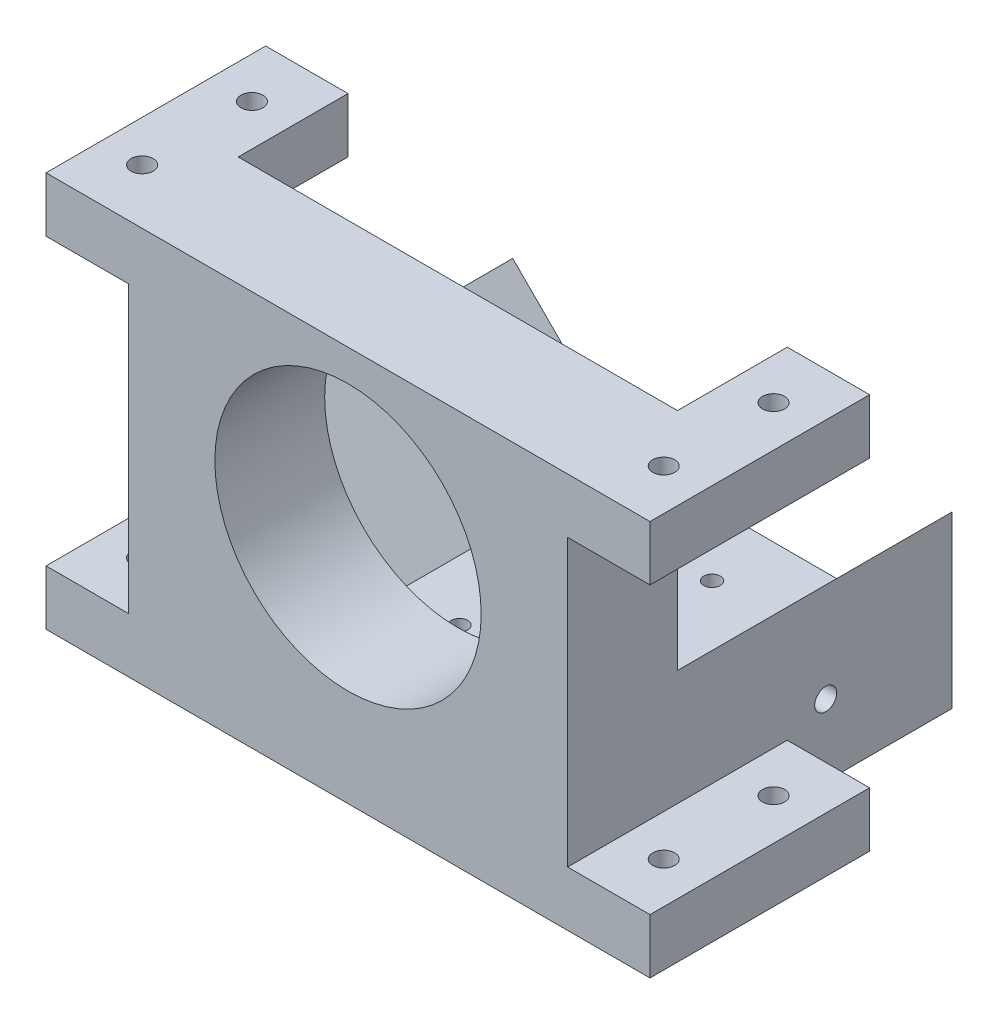
SolidWorks part; units mm, degrees
ref_plane "Front Plane" through (0, 0, 0) normal (0, 0, 1) x (1, 0, 0)
ref_plane "Top Plane" through (0, 0, 0) normal (0, 1, 0) x (1, 0, 0)
ref_plane "Right Plane" through (0, 0, 0) normal (1, 0, 0) x (0, 0, -1)
sketch "Sketch1" plane through (0, 0, 0) normal (0, 0, 1) x (1, 0, 0)
  line L1 (-40, -30) -> (40, -30)
  line L2 (-40, -30) -> (-40, 30)
  line L3 (-40, 30) -> (40, 30)
  line L4 (40, -30) -> (40, 30)
  line L5 (-40, -30) -> (40, 30) construction
  line L6 (-40, 30) -> (40, -30) construction
  circle A0 centre (0, 0) radius 24.25
  dimension "D1" = 48.5
  dimension "D2" = 80
  dimension "D3" = 60
extrude "Boss-Extrude1" add sketch "Sketch1" along normal blind 20
sketch "Sketch4" plane through (40, 0, 0) normal (1, 0, 0) x (0, 0, -1)
  line L0 (0, -30) -> (0, 30) construction
  line L1 (-20, 30) -> (0, 30)
  line L2 (-20, 30) -> (-20, 20)
  line L3 (-20, 20) -> (0, 20)
  line L5 (-20, 30) -> (0, 20) construction
  line L6 (-20, 20) -> (0, 30) construction
  line L8 (0, 30) -> (20, 30)
  line L10 (0, 20) -> (20, 20)
  line L11 (20, 30) -> (20, 20)
  line L12 (0, 30) -> (20, 20) construction
  line L13 (0, 20) -> (20, 30) construction
  point P4 (-10, 25)
  point P10 (10, 25)
  point P11 (-9.9994, 25.0003)
  point P12 (3.1904, 30)
  dimension "D1" = 10
extrude "Boss-Extrude3" add sketch "Sketch4" along normal blind 15
sketch "Sketch5" plane through (0, 30, 0) normal (0, 1, 0) x (1, 0, 0)
  line L0 (-40, -10) -> (55, -10) construction
  line L1 (55, 20) -> (55, -20) construction
  line L3 (40, 0) -> (40, -20) construction
  line L4 (40, 0) -> (-40, 0) construction
  line L5 (55, -20) -> (-40, -20) construction
  line L6 (-40, -20) -> (-40, 0) construction
  line L7 (55, 20) -> (55, -20) construction
  line L8 (40, 0) -> (55, 0) construction
  circle A0 centre (47.5, -10) radius 2
  circle A1 centre (47.5, 10) radius 2
  point P20 (0, 0)
  dimension "D1" = 4
  dimension "D2" = 7.5
extrude "Cut-Extrude2" cut sketch "Sketch5" against normal up to surface (10 mm away) up to face at (46, 20, 0)
sketch "Sketch6" plane through (0, -30, 0) normal (0, -1, 0) x (-1, 0, 0)
  line L1 (40, -20) -> (-40, -20)
  line L2 (40, -20) -> (40, 0)
  line L3 (40, 0) -> (-40, 0)
  line L4 (-40, -20) -> (-40, 0)
  line L5 (40, -20) -> (-40, 0) construction
  line L6 (40, 0) -> (-40, -20) construction
  point P4 (0, -10)
extrude "Boss-Extrude4" add sketch "Sketch6" along normal blind 2
sketch "Sketch8" plane through (0, 0, 0) normal (0, 0, -1) x (-1, 0, 0)
  line L0 (-40, -11) -> (-19, -32)
  line L1 (-40, -32) -> (-40, 20) construction
  line L2 (40, -32) -> (-40, -32) construction
  line L3 (-19, -32) -> (-40, -32)
  line L4 (-40, -32) -> (-40, -11)
  dimension "D1" = 21
extrude "Boss-Extrude6" add sketch "Sketch8" along normal blind 50
sketch "Sketch9" plane through (40, 0, 0) normal (1, 0, 0) x (0, 0, -1)
  line L0 (-20, -32) -> (-20, 20) construction
  line L1 (50, -32) -> (-20, -32) construction
  circle A0 centre (27, -29) radius 2
  dimension "D1" = 4
  dimension "D2" = 47
  dimension "D3" = 3
extrude "Cut-Extrude3" cut sketch "Sketch9" against normal through all
ref_plane "Plane1" through (19, 0, 0) normal (-1, 0, 0) x (0, 0, 1)
sketch "Sketch12" plane through (0, -32, 0) normal (0, -1, 0) x (1, 0, 0)
  line L0 (0, 20) -> (0, -50) construction
  line L1 (-40, 20) -> (40, 20)
  line L2 (-40, 20) -> (-40, -50)
  line L3 (-40, -50) -> (40, -50)
  line L4 (40, 20) -> (40, -50)
  line L5 (-40, 20) -> (40, -50) construction
  line L6 (-40, -50) -> (40, 20) construction
  line L7 (-8, -8.3) -> (8, -8.3) construction
  line L8 (-8, -8.3) -> (-8, -38.3) construction
  line L9 (-8, -38.3) -> (8, -38.3) construction
  line L10 (8, -38.3) -> (8, -8.3) construction
  line L11 (-40, 0) -> (19, 0) construction
  circle A0 centre (-8, -8.3) radius 1.5
  circle A1 centre (8, -8.3) radius 1.5
  circle A2 centre (8, -38.3) radius 1.5
  circle A3 centre (-8, -38.3) radius 1.5
  point P4 (0, -15)
  point P11 (0, -8.3)
  dimension "D4" = 3
  dimension "D1" = 16
  dimension "D2" = 30
  dimension "D3" = 8.3
extrude "Boss-Extrude8" add sketch "Sketch12" along normal blind 10
ref_plane "Plane2" through (0, 0, 0) normal (1, 0, 0) x (0, 0, -1)
mirror "Mirror1" about plane through (0, 0, 0) normal (1, 0, 0) of "Cut-Extrude3", "Boss-Extrude6", "Boss-Extrude4", "Cut-Extrude2", "Boss-Extrude3"
sketch "Sketch13" plane through (-40, 0, 0) normal (-1, 0, 0) x (0, 0, 1)
  line L0 (20, 20) -> (20, -42) construction
  line L1 (20, -42) -> (0, -42)
  line L2 (20, -42) -> (20, -32)
  line L3 (20, -32) -> (0, -32)
  line L5 (20, -42) -> (0, -32) construction
  line L6 (20, -32) -> (0, -42) construction
  line L7 (20, 20) -> (-20, 20) construction
  line L13 (-20, -42) -> (0, -42)
  line L14 (-20, -42) -> (-20, -32)
  line L15 (-20, -32) -> (0, -32)
  line L17 (-20, -42) -> (0, -32) construction
  line L18 (-20, -32) -> (0, -42) construction
  point P4 (10, -37)
  point P15 (-10, -37)
  dimension "D1" = 10
  dimension "D2" = 52
  dimension "D3" = 20
extrude "Boss-Extrude9" add sketch "Sketch13" along normal blind 15
sketch "Sketch14" plane through (0, -42, 0) normal (0, -1, 0) x (1, 0, 0)
  line L0 (-55, 0) -> (-27.8806, 0) construction
  circle A0 centre (-47.5, 10) radius 2
  circle A1 centre (-47.5, 10) radius 2 construction
  circle A2 centre (-47.5, -10) radius 2
extrude "Cut-Extrude4" cut sketch "Sketch14" against normal blind 10
mirror "Mirror2" about plane through (0, 0, 0) normal (1, 0, 0) of "Cut-Extrude4", "Boss-Extrude9"
